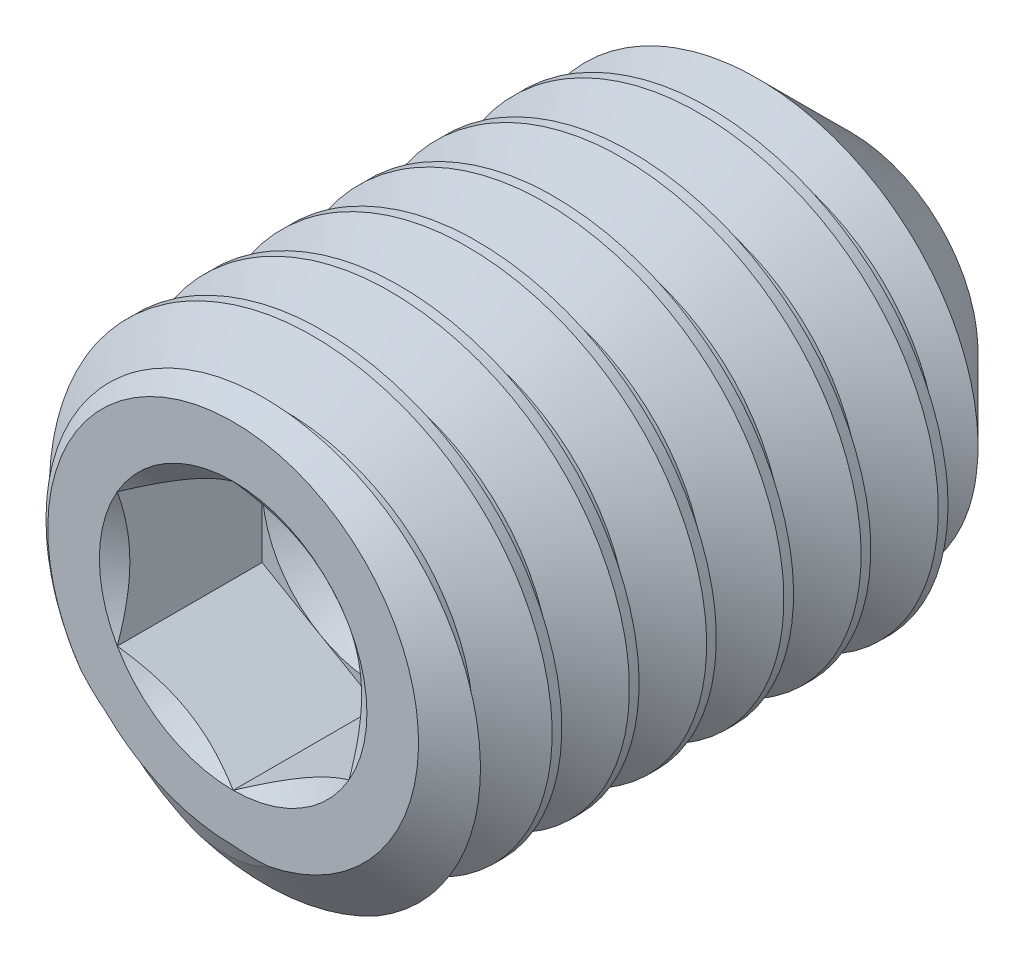
SolidWorks part; units mm, degrees
ref_plane "Front" through (0, 0, 0) normal (0, 0, 1) x (1, 0, 0)
ref_plane "Top" through (0, 0, 0) normal (0, 1, 0) x (1, 0, 0)
ref_plane "Right" through (0, 0, 0) normal (1, 0, 0) x (0, 0, -1)
sketch "Body Sketch" plane through (0, 0, 0) normal (1, 0, 0) x (0, 0, -1)
  line L0 (-1.7531, 0) -> (-1.7531, 1.2)
  line L1 (-1.7531, 1.2) -> (-1.543, 1.5)
  line L2 (-1.543, 1.5) -> (1.5689, 1.5)
  line L3 (1.5689, 1.5) -> (2.2469, 0.8219)
  line L4 (0.0129, 1.5) -> (0.0129, -1.5) construction
  line L5 (1.7531, 0) -> (-1.7531, 0)
  line L6 (-1.7531, 1.2) -> (-1.7531, -1.2) construction
  line L7 (1.7531, 0) -> (2.2469, 0.8219)
  line L8 (1.7531, 0) -> (2.2469, -0.8219) construction
  line L10 (1.7531, 0) -> (2.2469, 0) construction
  line L11 (2.2469, 0.8219) -> (2.2469, 0) construction
  point P11 (0.0129, 0)
  dimension "Length" = 4
  dimension "Top Chamfer" = 35
  dimension "Diameter" = 3
  dimension "D1" = 2.4
  dimension "D2" = 118
  dimension "D3" = 45
revolve "Body Revolve" add sketch "Body Sketch" angle 360 about L5
ref_plane "Bottom of Tip Plane" through (0, 0, -2.2469) normal (0, 0, 1) x (1, 0, 0)
sketch "Spiral Sketch" plane through (0, 0, -2.2469) normal (0, 0, 1) x (1, 0, 0)
  circle A0 centre (0, 0) radius 1.5 construction
  circle A1 centre (0, 0) radius 1.5
curve "Helix/Spiral" pitch 0.5 height 4.5 radius 1.5 centre (0, 0, -2.2469) axis (0, 0, 1) start towards (0, 1, 0) parameters "Thread Pitch"=0.5
sketch "Cut Sweep Sketch" plane through (0, 0, 0) normal (1, 0, 0) x (0, 0, -1)
  line L0 (2.2469, 1.5) -> (2.6844, 1.5)
  line L1 (2.6844, 1.5) -> (2.4969, 1.1752)
  line L2 (2.4969, 1.1752) -> (2.4344, 1.1752)
  line L3 (2.4344, 1.1752) -> (2.2469, 1.5)
  line L4 (2.3407, 1.3376) -> (2.5907, 1.3376) construction
  line L6 (-1.543, 1.5) -> (1.5689, 1.5) construction
  dimension "D1" = 0.0625
  dimension "D3" = 60
  dimension "D2" = 0.25
sweep "Cut Sweep" cut profiles "Cut Sweep Sketch" path "Helix/Spiral" align with end faces yes
sketch "Hex Sketch" plane through (0, 0, 1.7531) normal (0, 0, 1) x (1, 0, 0)
  line L1 (0, 0.866) -> (-0.75, 0.433)
  line L2 (-0.75, 0.433) -> (-0.75, -0.433)
  line L3 (-0.75, -0.433) -> (0, -0.866)
  line L4 (0, -0.866) -> (0.75, -0.433)
  line L5 (0.75, -0.433) -> (0.75, 0.433)
  line L6 (0.75, 0.433) -> (0, 0.866)
  circle A0 centre (0, 0) radius 0.75 construction
  dimension "Hex" = 1.5
extrude "Hex Extrude" cut sketch "Hex Sketch" against normal blind 0.9375
sketch "Hex Entry Sketch" plane through (0, 0, 1.7531) normal (0, 0, 1) x (1, 0, 0)
  circle A0 centre (0, 0) radius 0.866
extrude "Hex Entry Extrude" cut sketch "Hex Entry Sketch" against normal through all draft 55
sketch "Hex Bottom Sketch" plane through (0, 0, 0.8156) normal (0, 0, 1) x (1, 0, 0)
  circle A0 centre (0, 0) radius 0.75 construction
  circle A1 centre (0, 0) radius 0.75
extrude "Hex Bottom Extrude" cut sketch "Hex Bottom Sketch" against normal through all draft 60
ref_axis "Centerline Axis" through (0, 0, -1.7531) along (0, 0, 1)
equation "\"D1@Cut Sweep Sketch\" = \"Thread Pitch@Helix/Spiral\" * .125"
equation "\"D2@Cut Sweep Sketch\" = \"Thread Pitch@Helix/Spiral\" * .5"
equation "\"D3@Helix/Spiral\" = \"Length@Body Sketch\" + \"Thread Pitch@Helix/Spiral\""
equation "\"hex Depth@Hex Extrude\" = \"Hex@Hex Sketch\" * .625"
equation "\"D1@Body Sketch\" = \"Diameter@Body Sketch\" * .8"
equation "\"Diameter\"= 3mm"
equation "\"Thread Pitch\"= 0.5mm"
equation "\"Hex Size\"= 1.5mm"
equation "\"Diameter@Body Sketch\"=\"Diameter\""
equation "\"Thread Pitch@Helix/Spiral\"=\"Thread Pitch\""
equation "\"Hex@Hex Sketch\"=\"Hex Size\""
